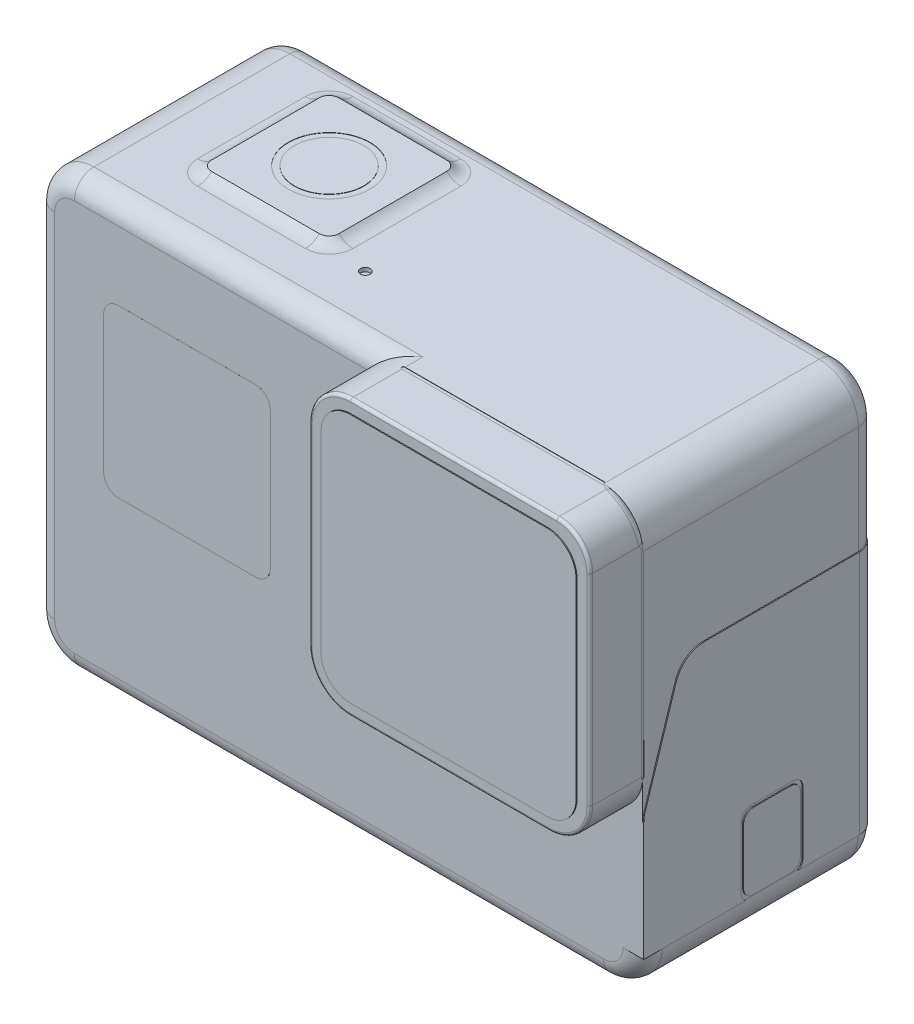
SolidWorks part; units mm, degrees
ref_plane "Front Plane" through (0, 0, 0) normal (0, 0, 1) x (1, 0, 0)
ref_plane "Top Plane" through (0, 0, 0) normal (0, 1, 0) x (1, 0, 0)
ref_plane "Right Plane" through (0, 0, 0) normal (1, 0, 0) x (0, 0, -1)
sketch "Sketch1" plane through (0, 0, 0) normal (0, 0, 1) x (1, 0, 0)
  line L1 (-27, -22) -> (27, -22)
  line L2 (-31, -18) -> (-31, 18)
  line L3 (-27, 22) -> (27, 22)
  line L4 (31, -18) -> (31, 18)
  line L5 (-31, -22) -> (31, 22) construction
  line L6 (-31, 22) -> (31, -22) construction
  arc A0 (-27, -22) -> (-31, -18) centre (-27, -18) cw
  arc A1 (27, -22) -> (31, -18) centre (27, -18) ccw
  arc A2 (27, 22) -> (31, 18) centre (27, 18) cw
  arc A3 (-31, 18) -> (-27, 22) centre (-27, 18) cw
  point P0 (0, 0)
  dimension "D3" = 4
  dimension "D1" = 62
  dimension "D2" = 44
extrude "Boss-Extrude1" add sketch "Sketch1" along normal blind 24
sketch "Sketch2" plane through (0, 0, 24) normal (0, 0, 1) x (1, 0, 0)
  line L3 (27, 22) -> (-27, 22) construction
  line L4 (31, -18) -> (31, 18) construction
  line L7 (27.6363, 22) -> (6.5797, 22)
  line L8 (31, 18.6363) -> (31, -1.884)
  line L9 (26.784, -6.1) -> (6.5797, -6.1)
  line L10 (2.3637, 17.784) -> (2.3637, -1.884)
  line L11 (31, 22) -> (2.3637, -6.1) construction
  line L12 (31, -6.1) -> (2.3637, 22) construction
  arc A0 (27.6363, 22) -> (31, 18.6363) centre (27.6363, 18.6363) cw
  arc A1 (31, -1.884) -> (26.784, -6.1) centre (26.784, -1.884) cw
  arc A2 (6.5797, -6.1) -> (2.3637, -1.884) centre (6.5797, -1.884) cw
  arc A3 (6.5797, 22) -> (2.3637, 17.784) centre (6.5797, 17.784) ccw
  point P0 (0, -2)
  point P21 (16.6819, 7.95)
  dimension "D1" = 0
  dimension "D2" = 0
sketch "Sketch3" plane through (0, 0, 24) normal (0, 0, 1) x (1, 0, 0)
  line L0 (-31, 18) -> (-31, -18) construction
  line L1 (-22.5, 13) -> (-8.5, 13)
  line L2 (-24, 11.5) -> (-24, -2.5)
  line L3 (-22.5, -4) -> (-8.5, -4)
  line L4 (-7, 11.5) -> (-7, -2.5)
  line L5 (-24, 13) -> (-7, -4) construction
  line L6 (-24, -4) -> (-7, 13) construction
  line L7 (27, 22) -> (-27, 22) construction
  arc A0 (-8.5, -4) -> (-7, -2.5) centre (-8.5, -2.5) ccw
  arc A1 (-24, -2.5) -> (-22.5, -4) centre (-22.5, -2.5) ccw
  arc A2 (-22.5, 13) -> (-24, 11.5) centre (-22.5, 11.5) ccw
  arc A3 (-8.5, 13) -> (-7, 11.5) centre (-8.5, 11.5) cw
  dimension "D5" = 1.5
  dimension "D1" = 17
  dimension "D2" = 17
  dimension "D3" = 7
  dimension "D4" = 9
extrude "Boss-Extrude6" add sketch "Sketch3" along normal blind 0.001
sketch "Sketch4" plane through (0, 22, 0) normal (0, 1, 0) x (1, 0, 0)
  line L0 (-27, -24) -> (-27, 0) construction
  line L1 (-9, -4) -> (-20, -4)
  line L2 (-8, -5) -> (-8, -16)
  line L3 (-9, -17) -> (-20, -17)
  line L4 (-21, -5) -> (-21, -16)
  line L5 (-8, -4) -> (-21, -17) construction
  line L6 (-8, -17) -> (-21, -4) construction
  line L7 (27, -24) -> (-27, -24) construction
  arc A0 (-20, -4) -> (-21, -5) centre (-20, -5) ccw
  arc A1 (-9, -4) -> (-8, -5) centre (-9, -5) cw
  arc A2 (-8, -16) -> (-9, -17) centre (-9, -16) cw
  arc A3 (-20, -17) -> (-21, -16) centre (-20, -16) cw
  point P0 (-14.5, -10.5)
  point P7 (-27, -12)
  point P8 (-14.5, -17)
  dimension "D5" = 1
  dimension "D1" = 13
  dimension "D2" = 13
  dimension "D3" = 6
  dimension "D4" = 7
sketch "Sketch9" plane through (0, 22, 0) normal (0, 1, 0) x (1, 0, 0)
  circle A0 centre (-3.9199, -17.384) radius 0.5
extrude "Cut-Extrude4" cut sketch "Sketch9" against normal blind 0.4
sketch "Sketch10" plane through (31, 0, 0) normal (1, 0, 0) x (0, 0, -1)
  line L0 (-24, -18) -> (-24, 18) construction
  line L1 (-17.8092, 7) -> (0, 7)
  line L2 (-24, -5.9684) -> (-24, -18)
  line L3 (-24, -18) -> (0, -18)
  line L4 (0, 7) -> (0, -18)
  line L5 (-20.9994, 3.8743) -> (0, -18) construction
  line L6 (-24, -18) -> (0, 7) construction
  line L7 (0, -18) -> (0, 18) construction
  line L8 (-24, -18) -> (0, -18) construction
  line L9 (-20.6664, 4.9146) -> (-23.8572, -5.0539)
  arc A0 (-23.8572, -5.0539) -> (-24, -5.9684) centre (-21, -5.9684) ccw
  arc A1 (-20.6664, 4.9146) -> (-17.8092, 7) centre (-17.8092, 4) cw
  dimension "D5" = 3
  dimension "D1" = 0
  dimension "D2" = 0
  dimension "D3" = 0
  dimension "D4" = 25
extrude "Boss-Extrude9" add sketch "Sketch10" along normal blind 0.1
sketch "Sketch11" plane through (31.1, 0, 0) normal (1, 0, 0) x (0, 0, -1)
  line L1 (-24, -18) -> (0, -18) construction
  line L2 (-12.8, -17.85) -> (-9, -17.85)
  line L3 (-13.8, -16.85) -> (-13.8, -11.15)
  line L4 (-12.8, -10.15) -> (-9, -10.15)
  line L5 (-8, -16.85) -> (-8, -11.15)
  line L6 (-13.8, -17.85) -> (-8, -10.15) construction
  line L8 (-13.8, -10.15) -> (-8, -17.85) construction
  line L9 (0, -18) -> (0, 7) construction
  line L11 (-13.0488, -18.1624) -> (-8.7512, -18.1624)
  line L12 (-14.0488, -17.1624) -> (-14.0488, -10.8376)
  line L13 (-13.0488, -9.8376) -> (-8.7512, -9.8376)
  line L14 (-7.7512, -17.1624) -> (-7.7512, -10.8376)
  line L15 (-14.0488, -18.1624) -> (-7.7512, -9.8376) construction
  line L16 (-14.0488, -9.8376) -> (-7.7512, -18.1624) construction
  arc A0 (-12.8, -17.85) -> (-13.8, -16.85) centre (-12.8, -16.85) cw
  arc A1 (-13.0488, -18.1624) -> (-14.0488, -17.1624) centre (-13.0488, -17.1624) cw
  arc A2 (-9, -17.85) -> (-8, -16.85) centre (-9, -16.85) ccw
  arc A3 (-8.7512, -18.1624) -> (-7.7512, -17.1624) centre (-8.7512, -17.1624) ccw
  arc A4 (-9, -10.15) -> (-8, -11.15) centre (-9, -11.15) cw
  arc A5 (-8.7512, -9.8376) -> (-7.7512, -10.8376) centre (-8.7512, -10.8376) cw
  arc A6 (-13.8, -11.15) -> (-12.8, -10.15) centre (-12.8, -11.15) cw
  arc A7 (-14.0488, -10.8376) -> (-13.0488, -9.8376) centre (-13.0488, -10.8376) cw
  point P0 (-10.9, -14)
  point P9 (-10.9, -14)
  dimension "D5" = 1
  dimension "D1" = 4
  dimension "D2" = 8
  dimension "D3" = 7.7
  dimension "D4" = 5.8
extrude "Cut-Extrude6" cut sketch "Sketch11" against normal blind 0.1
sketch "Sketch12" plane through (-31, 0, 0) normal (-1, 0, 0) x (0, 0, 1)
  line L0 (24, -18) -> (0, -18) construction
  line L1 (9, -6.4) -> (16, -6.4)
  line L2 (8, -7.4) -> (8, -13)
  line L3 (9, -14) -> (16, -14)
  line L4 (17, -7.4) -> (17, -13)
  line L5 (8, -6.4) -> (17, -14) construction
  line L6 (8, -14) -> (17, -6.4) construction
  line L8 (24, 18) -> (24, -18) construction
  line L13 (17.2533, -13.3605) -> (17.2533, -7.0395)
  line L14 (7.7467, -14.3605) -> (17.2533, -6.0395) construction
  line L15 (7.7467, -6.0395) -> (17.2533, -14.3605) construction
  arc A1 (16, -14) -> (17, -13) centre (16, -13) ccw
  arc A3 (8, -13) -> (9, -14) centre (9, -13) ccw
  arc A5 (9, -6.4) -> (8, -7.4) centre (9, -7.4) ccw
  arc A6 (16, -6.4) -> (17, -7.4) centre (16, -7.4) cw
  point P8 (12.5, -10.2)
  dimension "D1" = 4
  dimension "D2" = 7.6
  dimension "D3" = 9
  dimension "D4" = 7
extrude "Boss-Extrude10" add sketch "Sketch12" along normal blind 0.6 contours A6 L1 A5 L2 A3 L3 A1 L4 region at (-31, -10.2, 12.5)
extrude "Boss-Extrude11" add sketch "Sketch4" along normal blind 0.6
fillet "Fillet3" radius 0.3 8 edges at (-31, -6.6929, 16.7071) (-31, -6.4, 12.5) (-31, -6.6929, 8.2929) (-31, -10.2, 8) (-31, -13.7071, 8.2929) (-31, -14, 12.5) (-31, -13.7071, 16.7071) (-31, -10.2, 17)
sketch "Sketch15" plane through (-31, 0, 0) normal (-1, 0, 0) x (0, 0, 1)
  line L0 (24, 22) -> (0, 22) construction
  line L1 (24, 18) -> (24, -18) construction
  circle A0 centre (14.5, 15) radius 0.5
  dimension "D1" = 7
  dimension "D2" = 9.5
  dimension "D3" = 1
extrude "Cut-Extrude9" cut sketch "Sketch15" against normal blind 0.4
fillet "Fillet5" radius 2 8 edges at (-8.2929, 22, 16.7071) (-14.5, 22, 17) (-20.7071, 22, 16.7071) (-21, 22, 10.5) (-20.7071, 22, 4.2929) (-14.5, 22, 4) (-8.2929, 22, 4.2929) (-8, 22, 10.5)
extrude "Boss-Extrude12" add sketch "Sketch2" along normal blind 5.4
fillet "Fillet6" radius 1 3 edges at (31, 18.3181, 24) (27.3181, 22, 24) (30.0148, 21.0148, 24)
fillet "Fillet7" radius 2 14 edges at (-10.2102, 22, 24) (29.8284, -20.8284, 24) (0, -22, 24) (-29.8284, -20.8284, 24) (-31, 0, 24) (31, 12.5, 0) (29.8284, 20.8284, 0) (0, 22, 0) (29.8284, -20.8284, 0) (0, -22, 0) (-29.8284, -20.8284, 0) (-31, 0, 0) (-29.8284, 20.8284, 24) (-29.8284, 20.8284, 0)
fillet "Fillet8" radius 2 1 edges at (31.1, -5.5, 0)
fillet "Fillet10" radius 0.3 8 edges at (31, 8.3761, 29.4) (29.7652, -4.8652, 29.4) (16.6819, -6.1, 29.4) (3.5985, -4.8652, 29.4) (2.3637, 7.95, 29.4) (3.5985, 20.7652, 29.4) (17.108, 22, 29.4) (30.0148, 21.0148, 29.4)
sketch "Sketch18" plane through (0, -22, 0) normal (0, -1, 0) x (-1, 0, 0)
  line L0 (27, -22) -> (27, -2) construction
  line L1 (27, -22) -> (-13, -22)
  line L2 (27, -22) -> (27, -2)
  line L3 (27, -2) -> (-13, -2)
  line L4 (-13, -22) -> (-13, -2)
  line L5 (27, -22) -> (-13, -2) construction
  line L6 (27, -2) -> (-13, -22) construction
  line L7 (-27, -22) -> (27, -22) construction
  line L8 (27, -2) -> (-27, -2) construction
  point P4 (7, -12)
  dimension "D1" = 0
  dimension "D2" = 0
  dimension "D3" = 0
  dimension "D4" = 40
extrude "Boss-Extrude13" add sketch "Sketch18" along normal blind 0.1
sketch "Sketch19" plane through (0, -22.1, 0) normal (0, -1, 0) x (-1, 0, 0)
  line L0 (27, -22) -> (27, -2) construction
  line L1 (-4, -14) -> (4, -14)
  line L2 (-5, -13) -> (-5, -9)
  line L3 (-4, -8) -> (4, -8)
  line L4 (5, -13) -> (5, -9)
  line L6 (4.2038, -14.3458) -> (-4.2038, -14.3458)
  line L7 (27, -2) -> (-13, -2) construction
  line L8 (5.2038, -13.3458) -> (5.2038, -8.6542)
  line L9 (4.2038, -7.6542) -> (-4.2038, -7.6542)
  line L10 (-5.2038, -13.3458) -> (-5.2038, -8.6542)
  line L11 (5.2038, -14.3458) -> (-5.2038, -7.6542) construction
  line L12 (5.2038, -7.6542) -> (-5.2038, -14.3458) construction
  arc A0 (4, -8) -> (5, -9) centre (4, -9) cw
  arc A1 (4, -14) -> (5, -13) centre (4, -13) ccw
  arc A2 (-4, -14) -> (-5, -13) centre (-4, -13) cw
  arc A3 (-5, -9) -> (-4, -8) centre (-4, -9) cw
  arc A4 (4.2038, -14.3458) -> (5.2038, -13.3458) centre (4.2038, -13.3458) ccw
  arc A5 (5.2038, -8.6542) -> (4.2038, -7.6542) centre (4.2038, -8.6542) ccw
  arc A6 (-4.2038, -7.6542) -> (-5.2038, -8.6542) centre (-4.2038, -8.6542) ccw
  arc A7 (-4.2038, -14.3458) -> (-5.2038, -13.3458) centre (-4.2038, -13.3458) cw
  point P0 (0, -11)
  point P4 (0, -11)
  dimension "D5" = 1
  dimension "D3" = 1
  dimension "D1" = 22
  dimension "D2" = 6
  dimension "D4" = 6
extrude "Cut-Extrude13" cut sketch "Sketch19" against normal blind 0.1
sketch "Sketch22" plane through (0, 0, 0) normal (0, 0, -1) x (-1, 0, 0)
  line L0 (27, 20) -> (-27, 20) construction
  line L1 (-24.1, -15) -> (20.5, -15)
  line L2 (-24.1, -15) -> (-24.1, 15)
  line L3 (-24.1, 15) -> (20.5, 15)
  line L4 (20.5, -15) -> (20.5, 15)
  line L5 (-24.1, -15) -> (20.5, 15) construction
  line L6 (-24.1, 15) -> (20.5, -15) construction
  line L7 (29, -18) -> (29, 18) construction
  line L8 (-29.1, 7) -> (-29.1, -18) construction
  line L9 (-27, -20) -> (27, -20) construction
  point P0 (-1.8, 0)
  dimension "D1" = 5
  dimension "D2" = 8.5
  dimension "D3" = 5
  dimension "D4" = 5
extrude "Boss-Extrude15" add sketch "Sketch22" along normal blind 0.01
sketch "Sketch23" plane through (0, 0, 29.4) normal (0, 0, 1) x (1, 0, 0)
  line L0 (2.6637, 17.784) -> (2.6637, -1.884) construction
  line L1 (6.6637, -4.8) -> (26.7, -4.8)
  line L2 (3.6637, -1.8) -> (3.6637, 17.7)
  line L3 (6.6637, 20.7) -> (26.7, 20.7)
  line L4 (29.7, -1.8) -> (29.7, 17.7)
  line L5 (3.6637, -4.8) -> (29.7, 20.7) construction
  line L6 (3.6637, 20.7) -> (29.7, -4.8) construction
  line L7 (27.6363, 21.7) -> (6.5797, 21.7) construction
  line L8 (30.7, -1.884) -> (30.7, 18.6363) construction
  line L9 (6.5797, -5.8) -> (26.784, -5.8) construction
  arc A0 (26.7, -4.8) -> (29.7, -1.8) centre (26.7, -1.8) ccw
  arc A1 (26.7, 20.7) -> (29.7, 17.7) centre (26.7, 17.7) cw
  arc A2 (3.6637, 17.7) -> (6.6637, 20.7) centre (6.6637, 17.7) cw
  arc A3 (6.6637, -4.8) -> (3.6637, -1.8) centre (6.6637, -1.8) cw
  dimension "D5" = 3
  dimension "D6" = 3
  dimension "D1" = 1
  dimension "D2" = 1
  dimension "D3" = 1
  dimension "D4" = 1
extrude "Cut-Extrude15" cut sketch "Sketch23" against normal blind 5.4
sketch "Sketch25" plane through (0, 0, 24) normal (0, 0, 1) x (1, 0, 0)
  line L3 (3.6637, 17.7) -> (3.6637, -1.8) construction
  circle A0 centre (16, 8) radius 8.5
  dimension "D1" = 12.3363
  dimension "D3" = 17
extrude "Cut-Extrude16" cut sketch "Sketch25" against normal blind 5.4
sketch "Sketch26" plane through (0, 0, 18.6) normal (0, 0, 1) x (1, 0, 0)
  line L0 (16, 16.5) -> (16, -0.5)
  arc A0 (16, 16.5) -> (16, -0.5) centre (16, 8) ccw
  circle A1 centre (16, 8) radius 8.5 construction
  dimension "D1" = 17
  dimension "D2" = 0
revolve "Revolve2" add sketch "Sketch26" angle 360 about L0
sketch "Sketch28" plane through (-31.6, 0, 0) normal (-1, 0, 0) x (0, 0, 1)
  text T0 "mode" font "Century Gothic" height 1.5
extrude "Boss-Extrude16" add sketch "Sketch28" along normal blind 0.1
sketch "Sketch29" plane through (0, 22, 0) normal (0, 1, 0) x (1, 0, 0)
  line L0 (26.8816, -23.9552) -> (6.551, -23.9876) construction
  line L1 (26.8819, -24.1174) -> (6.5513, -24.1498)
  line L2 (26.8813, -23.793) -> (6.5508, -23.8255)
  arc A0 (26.8819, -24.1174) -> (26.8813, -23.793) centre (26.8816, -23.9552) ccw
  arc A1 (6.5508, -23.8255) -> (6.5513, -24.1498) centre (6.551, -23.9876) ccw
  point P2 (16.7163, -23.9714)
  point P7 (0, 0)
extrude "Cut-Extrude17" cut sketch "Sketch29" against normal blind 0.03
sketch "Sketch30" plane through (31, 0, 0) normal (1, 0, 0) x (0, 0, -1)
  line L0 (-24.0202, 17.9999) -> (-24.0007, -1.9646) construction
  line L1 (-23.9101, 18) -> (-23.8906, -1.9645)
  line L2 (-24.1304, 17.9998) -> (-24.1108, -1.9647)
  arc A0 (-23.9101, 18) -> (-24.1304, 17.9998) centre (-24.0202, 17.9999) ccw
  arc A1 (-24.1108, -1.9647) -> (-23.8906, -1.9645) centre (-24.0007, -1.9646) ccw
  point P2 (-24.0105, 8.0176)
  point P7 (0, 0)
extrude "Cut-Extrude18" cut sketch "Sketch30" against normal blind 0.03
sketch "Sketch32" plane through (0, 22.6, 0) normal (0, 1, 0) x (1, 0, 0)
  line L0 (-9, -4) -> (-20, -4) construction
  line L2 (-21, -5) -> (-21, -16) construction
  circle A0 centre (-14.5, -10.5) radius 3.5499
  circle A1 centre (-14.5, -10.5) radius 4.1536
  dimension "D1" = 6.5
  dimension "D2" = 6.5
extrude "Cut-Extrude19" cut sketch "Sketch32" against normal blind 0.03
sketch "Sketch34" plane through (0, 0, 29.4) normal (0, 0, 1) x (1, 0, 0)
  line L0 (26.7, 20.7) -> (6.6637, 20.7) construction
  line L1 (6.6637, 20.7) -> (26.7, 20.7)
  line L2 (3.6637, 17.7) -> (3.6637, -1.8)
  line L3 (6.6637, -4.8) -> (26.7, -4.8)
  line L4 (29.7, 17.7) -> (29.7, -1.8)
  line L5 (3.6637, 20.7) -> (29.7, -4.8) construction
  line L6 (3.6637, -4.8) -> (29.7, 20.7) construction
  line L7 (6.6637, -4.8) -> (26.7, -4.8) construction
  line L8 (3.6637, 17.7) -> (3.6637, -1.8) construction
  line L9 (29.7, -1.8) -> (29.7, 17.7) construction
  arc A0 (26.7, -4.8) -> (29.7, -1.8) centre (26.7, -1.8) ccw
  arc A1 (3.6637, -1.8) -> (6.6637, -4.8) centre (6.6637, -1.8) ccw
  arc A2 (6.6637, 20.7) -> (3.6637, 17.7) centre (6.6637, 17.7) ccw
  arc A3 (26.7, 20.7) -> (29.7, 17.7) centre (26.7, 17.7) cw
  point P4 (16.6819, 7.95)
  dimension "D5" = 3
  dimension "D1" = 0
  dimension "D2" = 0
  dimension "D3" = 0
  dimension "D4" = 0
extrude "Boss-Extrude18" add sketch "Sketch34" against normal blind 1 and the other way blind 0.1
equation "\"1צצ\"=2"
equation "\"0ץ\"=4"
